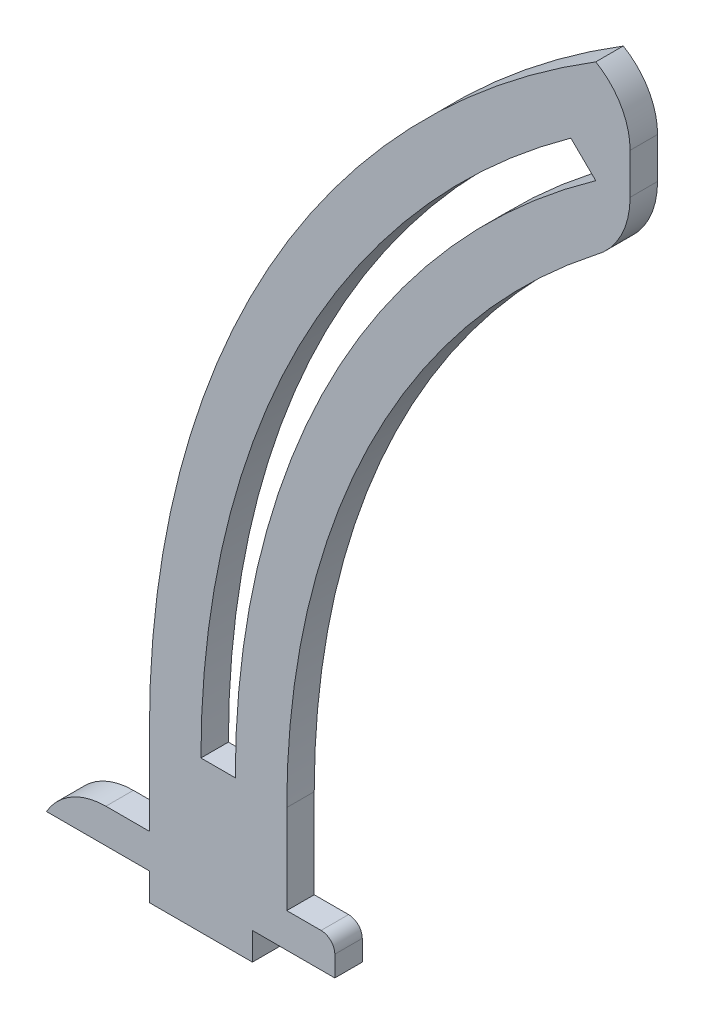
SolidWorks part; units mm, degrees
ref_plane "Front Plane" through (0, 0, 0) normal (0, 0, 1) x (1, 0, 0)
ref_plane "Top Plane" through (0, 0, 0) normal (0, 1, 0) x (1, 0, 0)
ref_plane "Right Plane" through (0, 0, 0) normal (1, 0, 0) x (0, 0, -1)
sketch "Sketch7" plane through (0, 0, 0) normal (0, 0, 1) x (1, 0, 0)
  arc A0 (-173.99, 0) -> (0, 173.99) centre (0, 0) cw
  dimension "D1" = 173.99
extrude "Extrude-Thin2" add sketch "Sketch7" along normal blind 5.08 thin contours A0 thin type one direction wall 25.4
sketch "Sketch8" plane through (0, 0, 5.08) normal (0, 0, 1) x (1, 0, 0)
  line L2 (-148.59, 0) -> (-173.99, 0) construction
  line L3 (0, 173.99) -> (0, 148.59) construction
  arc A0 (-164.465, 0) -> (0, 164.465) centre (0, 0) cw
  dimension "D1" = 164.465
extrude "Cut-Extrude-Thin3" cut sketch "Sketch8" against normal blind 5.08 and the other way through all flip side to cut thin thin type one direction wall 6.35
sketch "Sketch9" plane through (0, 0, 0) normal (0, -1, 0) x (1, 0, 0)
  line L1 (-173.99, 5.08) -> (-148.59, 5.08)
  line L2 (-173.99, 5.08) -> (-173.99, 0)
  line L3 (-173.99, 0) -> (-148.59, 0)
  line L4 (-148.59, 5.08) -> (-148.59, 0)
extrude "Boss-Extrude3" add sketch "Sketch9" along normal blind 22.86
sketch "Sketch10" plane through (-173.99, 0, 0) normal (-1, 0, 0) x (0, 0, 1)
  line L0 (5.08, -22.86) -> (5.08, 0) construction
  line L1 (0, -22.86) -> (5.08, -22.86)
  line L2 (0, -22.86) -> (0, -16.51)
  line L3 (0, -16.51) -> (5.08, -16.51)
  line L4 (5.08, -22.86) -> (5.08, -16.51)
  dimension "D1" = 6.35
extrude "Boss-Extrude4" add sketch "Sketch10" along normal blind 19.05 and the other way blind 34.29
sketch "Sketch11" plane through (0, -22.86, 0) normal (0, -1, 0) x (1, 0, 0)
  line L0 (-193.04, 5.08) -> (-161.29, 5.08) construction
  line L3 (-139.7, 5.08) -> (-193.04, 5.08) construction
  line L8 (-161.29, 5.08) -> (-161.29, 0) construction
  line L9 (-193.04, 0) -> (-139.7, 0) construction
  line L11 (-167.64, 0) -> (-154.94, 0)
  line L12 (-167.64, 0) -> (-167.64, 5.08)
  line L13 (-167.64, 5.08) -> (-154.94, 5.08)
  line L14 (-154.94, 0) -> (-154.94, 5.08)
  line L15 (-167.64, 0) -> (-154.94, 5.08) construction
  line L16 (-167.64, 5.08) -> (-154.94, 0) construction
  point P4 (-161.29, 2.54)
  dimension "D1" = 31.75
  dimension "D2" = 12.7
extrude "Boss-Extrude5" add sketch "Sketch11" along normal blind 5.08
sketch "Sketch12" plane through (0, 0, 5.08) normal (0, 0, 1) x (1, 0, 0)
  line L0 (-91.4322, -22.86) -> (-193.04, -22.86) construction
  line L2 (-91.4322, -22.86) -> (77.3812, -22.86)
  line L3 (-91.4322, -22.86) -> (-91.4322, 197.3778)
  line L4 (-91.4322, 197.3778) -> (77.3812, 197.3778)
  line L5 (77.3812, -22.86) -> (77.3812, 197.3778)
  dimension "D1" = 101.6078
extrude "Cut-Extrude1" cut sketch "Sketch12" against normal through all contours L3 L4 L5 L2
sketch "Sketch13" plane through (-91.4322, 0, 0) normal (1, 0, 0) x (0, 0, -1)
  line L1 (-5.08, 148.0293) -> (0, 148.0293)
  line L2 (-5.08, 148.0293) -> (-5.08, 117.1287)
  line L3 (-5.08, 117.1287) -> (0, 117.1287)
  line L4 (0, 148.0293) -> (0, 117.1287)
extrude "Boss-Extrude6" add sketch "Sketch13" along normal blind 6.35
fillet "Fillet2" radius 15.24 1 edges at (-85.0822, 117.1287, 2.54)
fillet "Fillet3" radius 12.7 1 edges at (-85.0822, 148.0293, 2.54)
fillet "Fillet4" radius 12.7 1 edges at (-193.04, -16.51, 2.54)
fillet "Fillet5" radius 2.54 1 edges at (-139.7, -16.51, 2.54)
sketch "Sketch15" plane through (0, 0, 0) normal (0, 0, 1) x (1, 0, 0)
  line L0 (-91.4322, 128.9981) -> (-96.0426, 133.5086)
  line L3 (-96.0426, 133.5086) -> (-90.0117, 142.9111)
  line L4 (-90.0117, 142.9111) -> (-86.2174, 133.7831)
  line L5 (-86.2174, 133.7831) -> (-91.4322, 128.9981)
  arc A0 (-91.4322, 136.7073) -> (-164.465, 0) centre (0, 0) ccw construction
extrude "Boss-Extrude14" add sketch "Sketch15" along normal blind 5.08 contours L0 L3 L4 L5
sketch "Sketch16" plane through (-167.64, 0, 0) normal (-1, 0, 0) x (0, 0, 1)
  line L1 (0, -27.94) -> (5.08, -27.94)
  line L2 (0, -27.94) -> (0, -22.86)
  line L3 (0, -22.86) -> (5.08, -22.86)
  line L4 (5.08, -27.94) -> (5.08, -22.86)
extrude "Boss-Extrude15" add sketch "Sketch16" along normal blind 6.35
equation "\"Foamcore\" = .1in"
equation "\"MDF\" = .2in"
equation "\"Gmaterial\"= \"MDF\""
equation "\"PVC-ID\" = \"1.590in\""
equation "\"PVC-OD\" = \"1.900in\""
equation "\"PVC-Sleeve-Width\" = \".51in\""
equation "\"Arc-Radius\"= 6.35 + .5"
equation "\"D1@Sketch7\"=\"Arc-Radius\""
equation "\"D1@Extrude-Thin2\"=\"Gmaterial\""
equation "\"D1@Sketch8\"=\"Arc-Radius\"-.5+(\"Gmaterial\"+.05)/2"
equation "\"D5@Cut-Extrude-Thin3\"=\"Gmaterial\"+.05"
equation "\"D1@Boss-Extrude5\"=\"Gmaterial\""
equation "\"D1@Cut-Extrude-Thin3\"=\"Gmaterial\""
equation "\"D1@Boss-Extrude14\"=\"Gmaterial\""
